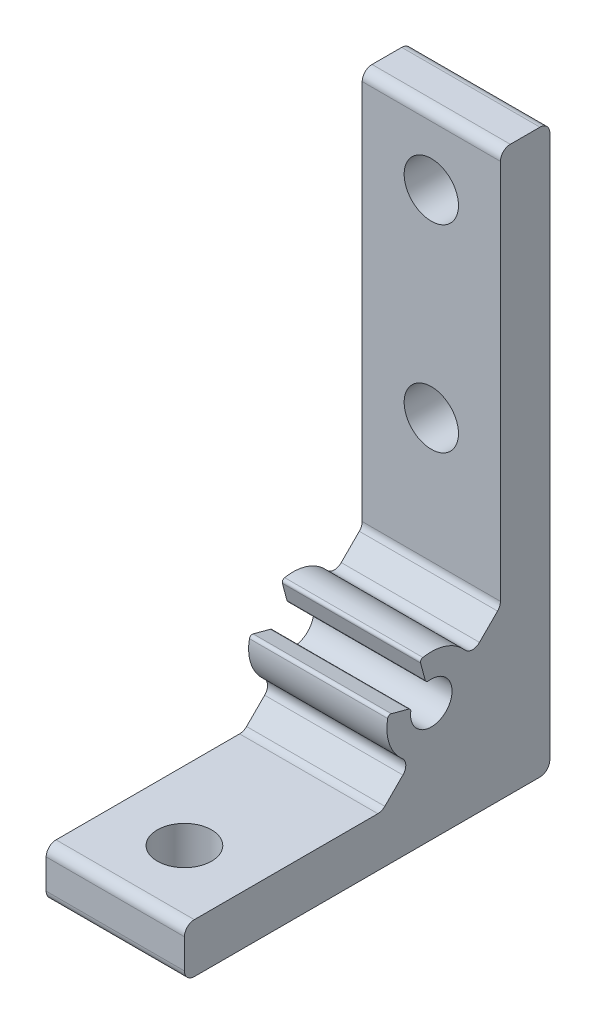
SolidWorks part; units mm, degrees
ref_plane "Front Plane" through (0, 0, 0) normal (0, 0, 1) x (1, 0, 0)
ref_plane "Top Plane" through (0, 0, 0) normal (0, 1, 0) x (1, 0, 0)
ref_plane "Right Plane" through (0, 0, 0) normal (1, 0, 0) x (0, 0, -1)
ref_plane "Plane1" through (0, 0, 0) normal (1, 0, 0) x (0, 0, -1)
sketch "Sketch1" plane through (0, 0, 0) normal (1, 0, 0) x (0, 0, -1)
  line L0 (-36, 0) -> (-1, 0)
  line L1 (0, 1) -> (0, 56)
  line L2 (-1, 57) -> (-4, 57)
  line L3 (-5, 56) -> (-5, 17.4142)
  line L4 (-5.2929, 16.7071) -> (-7.122, 14.878)
  line L5 (-13.0843, 16.0465) -> (-12.6163, 14.3)
  line L6 (-14.3, 12.6163) -> (-16.0465, 13.0843)
  line L7 (-14.878, 7.122) -> (-16.7071, 5.2929)
  line L8 (-17.4142, 5) -> (-36, 5)
  line L9 (-37, 4) -> (-37, 1)
  arc A0 (-37, 1) -> (-36, 0) centre (-36, 1) ccw
  arc A1 (-1, 0) -> (0, 1) centre (-1, 1) ccw
  arc A2 (0, 56) -> (-1, 57) centre (-1, 56) ccw
  arc A3 (-4, 57) -> (-5, 56) centre (-4, 56) ccw
  arc A4 (-5, 17.4142) -> (-5.2929, 16.7071) centre (-6, 17.4142) cw
  arc A5 (-7.122, 14.878) -> (-8.5874, 14.9333) centre (-7.8291, 15.5851) cw
  arc A6 (-8.5874, 14.9333) -> (-12.8512, 16.4188) centre (-12, 12) ccw
  arc A7 (-12.8512, 16.4188) -> (-13.0843, 16.0465) centre (-12.7945, 16.1242) ccw
  arc A8 (-12.6163, 14.3) -> (-12.2857, 14.0805) centre (-12.3265, 14.3777) ccw
  arc A9 (-12.2857, 14.0805) -> (-14.0805, 12.2857) centre (-12, 12) cw
  arc A10 (-14.0805, 12.2857) -> (-14.3, 12.6163) centre (-14.3777, 12.3265) ccw
  arc A11 (-16.0465, 13.0843) -> (-16.4188, 12.8512) centre (-16.1242, 12.7945) ccw
  arc A12 (-16.4188, 12.8512) -> (-14.9333, 8.5874) centre (-12, 12) ccw
  arc A13 (-14.9333, 8.5874) -> (-14.878, 7.122) centre (-15.5851, 7.8291) cw
  arc A14 (-16.7071, 5.2929) -> (-17.4142, 5) centre (-17.4142, 6) cw
  arc A15 (-36, 5) -> (-37, 4) centre (-36, 4) ccw
extrude "Boss-Extrude1" add sketch "Sketch1" against normal blind 7 and the other way blind 7
ref_plane "Plane2" through (0, 0, 0) normal (0, 0, 1) x (1, 0, 0)
sketch "Sketch2" plane through (0, 0, 0) normal (0, 0, 1) x (1, 0, 0)
  circle A0 centre (0, 30) radius 2.75
extrude "Cut-Extrude1" cut sketch "Sketch2" along normal blind 5
ref_plane "Plane3" through (0, 0, 0) normal (0, 0, 1) x (1, 0, 0)
sketch "Sketch3" plane through (0, 0, 0) normal (0, 0, 1) x (1, 0, 0)
  circle A0 centre (0, 50) radius 2.75
extrude "Cut-Extrude2" cut sketch "Sketch3" along normal blind 5
ref_plane "Plane4" through (0, 0, 0) normal (0, 1, 0) x (1, 0, 0)
sketch "Sketch4" plane through (0, 0, 0) normal (0, 1, 0) x (1, 0, 0)
  circle A0 centre (0, -30) radius 2.75
extrude "Cut-Extrude3" cut sketch "Sketch4" along normal blind 5
